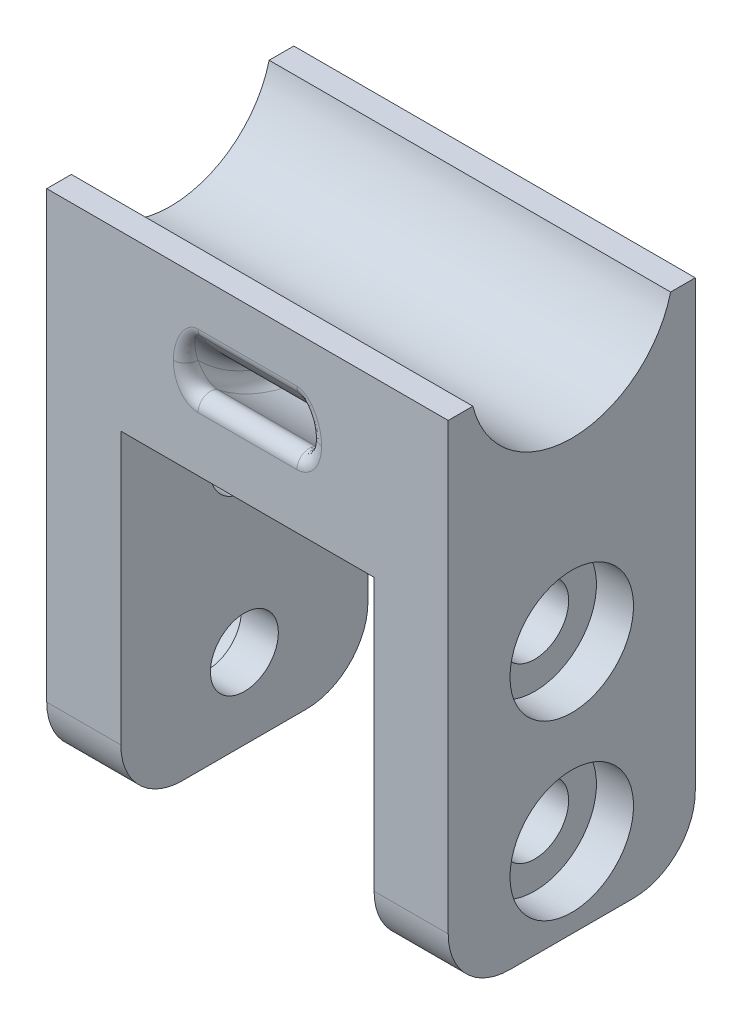
SolidWorks part; units mm, degrees
ref_plane "Спереди" through (0, 0, 0) normal (0, 0, 1) x (1, 0, 0)
ref_plane "Сверху" through (0, 0, 0) normal (0, 1, 0) x (1, 0, 0)
ref_plane "Справа" through (0, 0, 0) normal (1, 0, 0) x (0, 0, -1)
sketch "Эскиз1" plane through (0, 0, 0) normal (0, 1, 0) x (1, 0, 0)
  line L1 (-10, 10) -> (10, 10)
  line L2 (-10, 10) -> (-10, -10)
  line L3 (-10, -10) -> (10, -10)
  line L4 (10, 10) -> (10, -10)
  line L5 (-10, 10) -> (10, -10) construction
  line L6 (-10, -10) -> (10, 10) construction
  point P0 (0, 0)
  dimension "D1" = 20
  dimension "D2" = 20
extrude "Бобышка-Вытянуть1" add sketch "Эскиз1" along normal blind 14
sketch "Эскиз2" plane through (-10, 0, 0) normal (-1, 0, 0) x (0, 0, 1)
  line L0 (-10, 14) -> (10, 14) construction
  circle A0 centre (0, 16) radius 8.25
  dimension "D1" = 16.5
  dimension "D2" = 2
extrude "Вырез-Вытянуть1" cut sketch "Эскиз2" against normal through all
sketch "Эскиз3" plane through (0, 0, 0) normal (1, 0, 0) x (0, 0, -1)
  line L0 (-10, 14) -> (-10, 10) construction
  line L1 (-10, 14) -> (-10, 0) construction
  circle A0 centre (0, 16) radius 11.6619
  circle A1 centre (0, 16) radius 13.6619
  arc A2 (-8.0039, 14) -> (8.0039, 14) centre (0, 16) ccw construction
  dimension "D1" = 4
extrude "Вырез-Вытянуть2" cut sketch "Эскиз3" against normal mid plane 10
fillet "Скругление1" radius 1 8 edges at (0, 6.6915, -10) (5, 2.3381, 0) (0, 6.6915, 10) (-5, 2.3381, 0) (-5, 4.3381, 0) (0, 10, 10) (5, 4.3381, 0) (0, 10, -10)
sketch "Эскиз5" plane through (-10, 0, 0) normal (-1, 0, 0) x (0, 0, 1)
  line L0 (10, 14) -> (10, 0) construction
  line L1 (10, -27) -> (-10, -27)
  line L2 (10, -27) -> (10, 0)
  line L3 (10, 0) -> (-10, 0) construction
  line L4 (-10, -27) -> (-10, 0)
  line L5 (10, -27) -> (-10, 0) construction
  line L6 (10, 0) -> (-10, -27) construction
  line L7 (-10, -13.5) -> (10, -13.5) construction
  line L18 (10, 14) -> (8.0039, 14)
  line L19 (-8.0039, 14) -> (-10, 14)
  line L20 (-10, 14) -> (-10, 0)
  line L21 (-10, 0) -> (10, 0)
  line L22 (10, 0) -> (10, 14)
  line L23 (10, 14) -> (8.0039, 14)
  line L24 (-8.0039, 14) -> (-10, 14)
  line L25 (-10, 14) -> (-10, 0)
  line L26 (-10, 0) -> (10, 0) construction
  line L27 (10, 0) -> (10, 14)
  circle A0 centre (0, -6.5) radius 2.75
  circle A1 centre (0, -20.5) radius 2.75
  arc A4 (-8.0039, 14) -> (8.0039, 14) centre (0, 16) ccw
  arc A5 (-8.0039, 14) -> (8.0039, 14) centre (0, 16) ccw
  point P0 (0, -13.5)
  dimension "D2" = 5.5
  dimension "D1" = 27
  dimension "D3" = 14
  dimension "D4" = 0
extrude "Бобышка-Вытянуть2" add sketch "Эскиз5" along normal blind 6.25
sketch "Эскиз6" plane through (-10, 0, 0) normal (1, 0, 0) x (0, 0, -1)
  line L8 (10, -27) -> (10, 0)
  line L9 (10, 0) -> (-10, 0)
  line L10 (-10, 0) -> (-10, -27)
  line L11 (-10, -27) -> (10, -27)
  line L12 (10, -27) -> (10, 0)
  line L13 (10, 0) -> (-10, 0)
  line L14 (-10, 0) -> (-10, -27)
  line L15 (-10, -27) -> (10, -27)
  dimension "D1" = 0
extrude "Вырез-Вытянуть3" cut sketch "Эскиз6" against normal blind 0.25
sketch "Эскиз7" plane through (-16.25, 0, 0) normal (-1, 0, 0) x (0, 0, 1)
  circle A0 centre (0, -6.5) radius 5
  circle A1 centre (0, -20.5) radius 5
  dimension "D1" = 10
  dimension "D2" = 10
extrude "Вырез-Вытянуть4" cut sketch "Эскиз7" against normal blind 3
fillet "Скругление2" radius 5 2 edges at (-13.25, -27, -10) (-13.25, -27, 10)
mirror "Зеркальное отражение1" about plane through (0, 0, 0) normal (1, 0, 0) of "Вырез-Вытянуть3", "Скругление2", "Вырез-Вытянуть4", "Бобышка-Вытянуть2"
equation "\"print_offset\"= 0.5"
equation "\"screw_m5_d\"= 5"
equation "\"screw_m5_hh_d\"= 9.5"
equation "\"nut_m5_d\"= 7.9"
equation "\"nut_m5_h\"= 3.9"
equation "\"tube_d\"= 16"
equation "\"tube_tape_d\"= 2"
equation "\"tube_tape_h\"= 10"
equation "\"D2@Эскиз1\"=\"D1@Эскиз1\""
equation "\"D1@Эскиз2\"=\"tube_d\"+\"print_offset\""
equation "\"D2@Эскиз3\"=\"tube_tape_d\""
equation "\"D1@Вырез-Вытянуть2\"=\"tube_tape_h\""
equation "\"D2@Эскиз5\"=\"screw_m5_d\"+\"print_offset\""
equation "\"D1@Бобышка-Вытянуть2\"=\"print_offset\"/2+6"
equation "\"D1@Вырез-Вытянуть3\"=\"print_offset\"/2"
equation "\"D1@Эскиз7\"=\"screw_m5_hh_d\"+\"print_offset\""
equation "\"D2@Эскиз7\"=\"D1@Эскиз7\""
